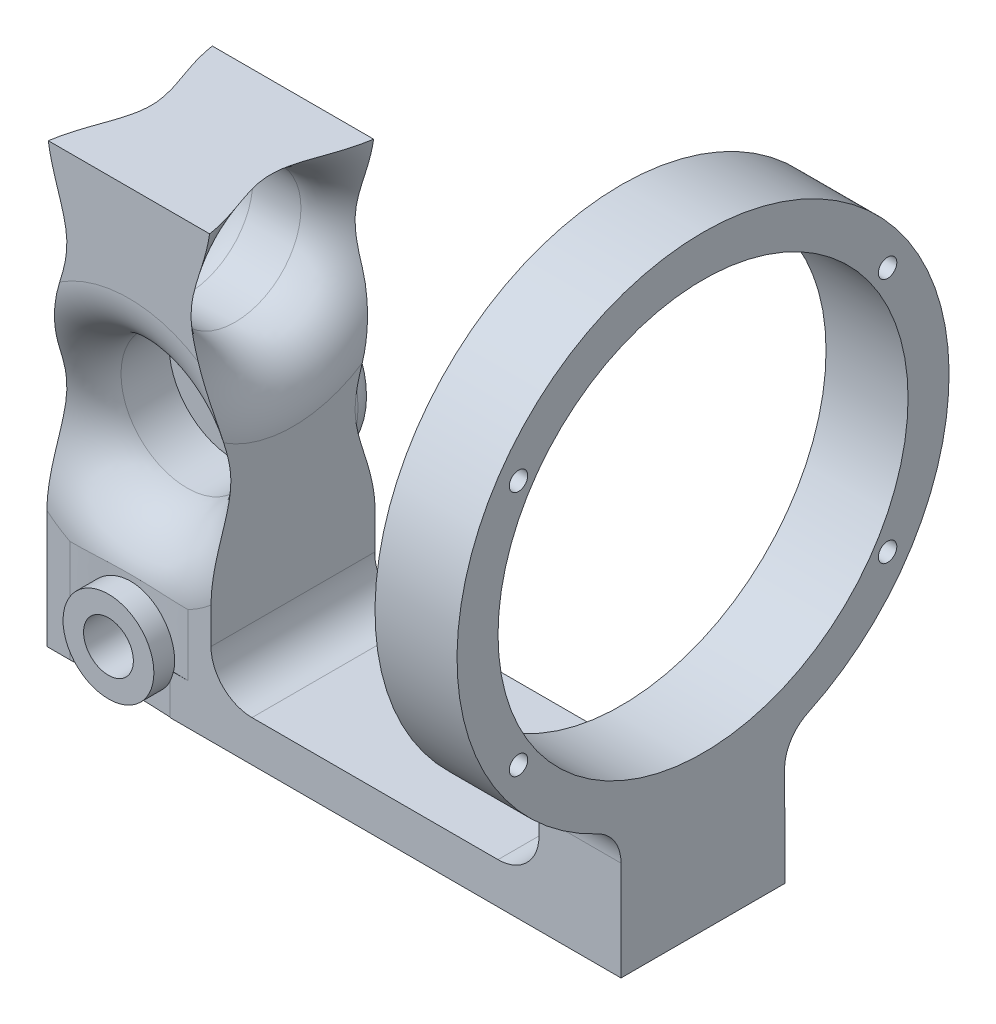
SolidWorks part; units mm, degrees
other "Markup1"
sketch "Sketch4" plane through (29.9294, 37, -10) normal (0.6492, 0.1556, -0.7445) x (-0.7605, 0.1488, -0.632)
ref_plane "Front Plane" through (0, 0, 0) normal (0, 0, 1) x (1, 0, 0)
ref_plane "Top Plane" through (0, 0, 0) normal (0, 1, 0) x (1, 0, 0)
ref_plane "Right Plane" through (0, 0, 0) normal (1, 0, 0) x (0, 0, -1)
sketch "Sketch1" plane through (0, 0, 0) normal (0, 0, 1) x (1, 0, 0)
  line L1 (20, -30) -> (-20, -30)
  line L2 (20, -30) -> (20, 30)
  line L3 (20, 30) -> (-20, 30)
  line L4 (-20, -30) -> (-20, 30)
  circle A0 centre (0, -17.5) radius 11.05
  point P0 (0, 0)
  dimension "D4" = 22.1
  dimension "D1" = 40
  dimension "D2" = 17.5
  dimension "D3" = 60
extrude "Boss-Extrude1" add sketch "Sketch1" along normal blind 40
sketch "Sketch2" plane through (-20, 0, 0) normal (-1, 0, 0) x (0, 0, 1)
  line L0 (40, 30) -> (0, 30) construction
  circle A0 centre (20, 17.5) radius 11.05
  dimension "D1" = 22.1
  dimension "D2" = 12.5
extrude "Cut-Extrude1" cut sketch "Sketch2" against normal blind 40 contours A0
fillet "Fillet1" radius 4 4 edges at (11.05, -17.5, 0) (11.05, -17.5, 40) (-20, 17.5, 31.05) (20, 17.5, 31.05)
sketch "Sketch3" plane through (0, 30, 0) normal (0, 1, 0) x (1, 0, 0)
  line L0 (-20, -20) -> (19.8588, -20)
  line L1 (-20, -4.95) -> (-20, -35.05) construction
  line L3 (29.9294, -50) -> (-30.0706, -50)
  line L4 (29.9294, -50) -> (29.9294, 10)
  line L5 (29.9294, 10) -> (-30.0706, 10)
  line L6 (-30.0706, -50) -> (-30.0706, 10)
  line L7 (29.9294, -50) -> (-30.0706, 10) construction
  line L8 (29.9294, 10) -> (-30.0706, -50) construction
  point P4 (-0.0706, -20)
  dimension "D1" = 60
extrude "Boss-Extrude2" add sketch "Sketch3" along normal blind 7
chamfer "Chamfer1" distance 1.75 angle 45 12 edges at (-0.0706, 37, -10) (-0.0706, 30, -10) (29.9294, 37, 20) (29.9294, 33.5, -10) (29.9294, 30, 20) (-0.0706, 37, 50) (29.9294, 33.5, 50) (-0.0706, 30, 50) (-30.0706, 33.5, -10) (-30.0706, 37, 20) (-30.0706, 33.5, 50) (-30.0706, 30, 20)
sketch "Sketch6" plane through (0, 30, 0) normal (0, -1, 0) x (-1, 0, 0)
  line L0 (20, -40) -> (-20, -40)
  line L1 (-20, -40) -> (-20, 0)
  line L2 (-20, 0) -> (20, 0)
  line L3 (20, 0) -> (20, -40)
  line L4 (36.5937, -52.5638) -> (-35.2538, -52.5638)
  line L5 (-35.2538, -52.5638) -> (-35.2538, 13.1087)
  line L6 (-35.2538, 13.1087) -> (36.5937, 13.1087)
  line L7 (36.5937, 13.1087) -> (36.5937, -52.5638)
extrude "Cut-Extrude3" cut sketch "Sketch6" against normal blind 100
sketch "Sketch7" plane through (20, 0, 0) normal (1, 0, 0) x (0, 0, -1)
  circle A0 centre (-20, 17.5) radius 16.05
  dimension "D1" = 32.1
extrude "Cut-Extrude4" cut sketch "Sketch7" against normal blind 100
fillet "Fillet2" radius 15 2 edges at (-20, 17.5, 3.95) (20, 17.5, 3.95)
sketch "Sketch12" plane through (0, -30, 0) normal (0, -1, 0) x (-1, 0, 0)
  line L0 (20, -40) -> (-20, -40)
  line L1 (-20, -40) -> (-20, 0)
  line L2 (-20, 0) -> (20, 0)
  line L3 (20, 0) -> (20, -40)
sketch "Sketch14" plane through (0, -30, 0) normal (0, -1, 0) x (-1, 0, 0)
  line L0 (20, -40) -> (-20, -40)
  line L1 (-20, -40) -> (-20, 0)
  line L2 (-20, 0) -> (20, 0)
  line L3 (20, 0) -> (20, -40)
extrude "Boss-Extrude5" add sketch "Sketch14" along normal blind 15
sketch "Sketch15" plane through (0, 0, 40) normal (0, 0, 1) x (1, 0, 0)
  circle A0 centre (0, -17.5) radius 16.05
  dimension "D1" = 32.1
extrude "Cut-Extrude7" cut sketch "Sketch15" against normal blind 100
fillet "Fillet3" radius 15 2 edges at (16.05, -17.5, 0) (16.05, -17.5, 40)
sketch "Sketch20" plane through (0, -45, 0) normal (0, -1, 0) x (-1, 0, 0)
  line L0 (20, 0) -> (-20, -40)
  line L2 (20, -40) -> (-20, 0)
  line L4 (20, 0) -> (-20, 0)
  line L5 (20, 0) -> (20, -40)
  line L6 (20, -40) -> (-20, -40)
  line L7 (-20, 0) -> (-20, -40)
  line L8 (20, 0) -> (-20, -40) construction
  line L9 (20, -40) -> (-20, 0) construction
  point P5 (0, -20)
extrude "Boss-Extrude7" add sketch "Sketch20" along normal blind 25
sketch "Sketch21" plane through (0, 0, 40) normal (0, 0, 1) x (1, 0, 0)
  line L0 (0, -57.5) -> (0, -45)
  line L1 (0, -57.5) -> (0, -70)
  line L2 (-14.4171, -70) -> (14.4171, -70) construction
  circle A0 centre (0, -57.5) radius 6.05
  spline S0 degree 3 poles (14.4171, -45) (12.0121, -45) (9.6108, -45) (6.0082, -45) (3.6062, -45) (1.2025, -45) (-1.2025, -45) (-3.6062, -45) (-6.0082, -45) (-9.6108, -45) (-12.0121, -45) (-14.4171, -45) knots 0 0 0 0 0.25 0.25 0.375 0.5 0.5 0.625 0.75 0.75 1 1 1 1 construction
  dimension "D1" = 12.1
extrude "Cut-Extrude11" cut sketch "Sketch21" against normal blind 10 contours L0 A0 L1 | L1 A0 L0
sketch "Sketch22" plane through (20, 0, 0) normal (1, 0, 0) x (0, 0, -1)
  line L0 (0, -70) -> (-40, -70) construction
  line L1 (0, -70) -> (0, -41.2508) construction
  line L2 (-40, -45) -> (0, -45)
  line L3 (-40, -70) -> (-40, -41.2508) construction
  line L4 (-20, -45) -> (-20, -57.5)
  line L5 (-20, -57.5) -> (0, -57.5)
  circle A1 centre (-20, -57.5) radius 6.05
  dimension "D1" = 12.1
  dimension "D2" = 25
  dimension "D3" = 12.5
  dimension "D4" = 20
extrude "Cut-Extrude12" cut sketch "Sketch22" against normal blind 10 contours L5 A1 L4 | L4 A1 L5
sketch "Sketch23" plane through (0, 0, 0) normal (0, 0, -1) x (-1, 0, 0)
  line L0 (20, -41.2508) -> (20, -70) construction
  circle A0 centre (0, -57.5) radius 6.05
  dimension "D3" = 12.1
  dimension "D1" = 20
  dimension "D2" = 12.5
extrude "Cut-Extrude18" cut sketch "Sketch23" against normal blind 10
sketch "Sketch24" plane through (-20, 0, 0) normal (-1, 0, 0) x (0, 0, 1)
  line L0 (40, -70) -> (0, -70) construction
  circle A0 centre (20, -57.5) radius 6.05
  dimension "D1" = 12.1
  dimension "D2" = 12.5
extrude "Cut-Extrude19" cut sketch "Sketch24" against normal blind 10
sketch "Sketch25" plane through (20, 0, 0) normal (1, 0, 0) x (0, 0, -1)
  circle A0 centre (-20, 17.5) radius 50
  circle A1 centre (-20, 17.5) radius 60
  dimension "D1" = 100
  dimension "D2" = 10
extrude "Boss-Extrude8" add sketch "Sketch25" along normal blind 20 from offset 80 separate body
sketch "Sketch26" plane through (120, 0, 0) normal (1, 0, 0) x (0, 0, -1)
  line L0 (-40, -70) -> (0, -70)
  line L1 (0, -70) -> (-0.1452, -38.4492)
  line L2 (-40, -70) -> (-40, -38.4492)
  line L3 (-40, -38.4492) -> (-0.1452, -38.4492)
  spline S0 degree 3 poles (-3.1059, -8.5517) (-3.5245, -9.8859) (-3.9276, -11.2231) (-4.5568, -13.9327) (-4.7791, -15.3059) (-4.8543, -17.0624) (-4.8594, -17.417) (-4.849, -18.1218) (-4.8337, -18.4722) (-4.7593, -19.5181) (-4.6714, -20.208) (-4.3178, -22.2606) (-3.9628, -23.6062) (-3.1703, -26.2815) (-2.7339, -27.6113) (-1.8977, -30.2783) (-1.4974, -31.6155) (-0.4659, -35.6628) (0, -38.4078) (0, -41.2508) knots 0 0 0 0 0.125 0.125 0.25 0.25 0.28125 0.28125 0.3125 0.3125 0.375 0.375 0.5 0.5 0.625 0.625 0.75 0.75 1 1 1 1 construction
extrude "Boss-Extrude9" add sketch "Sketch26" against normal blind 20
sketch "Sketch27" plane through (120, 0, 0) normal (1, 0, 0) x (0, 0, -1)
  line L6 (-40, -60) -> (-0.046, -60)
  line L7 (-40, -39.0685) -> (-40, -70) construction
  line L8 (0, -70) -> (-0.1421, -39.1186) construction
  line L9 (-40, -70) -> (0, -70) construction
  line L10 (-40, -60) -> (-40, -70)
  line L11 (-40, -70) -> (0, -70)
  line L12 (0, -70) -> (-0.046, -60)
  dimension "D1" = 10
extrude "Boss-Extrude11" add sketch "Sketch27" against normal blind 110
sketch "Sketch28" plane through (20, 0, 0) normal (1, 0, 0) x (0, 0, -1)
  circle A0 centre (-20, -57.5) radius 6.05
extrude "Boss-Extrude12" add sketch "Sketch28" against normal blind 30
sketch "Sketch29" plane through (120, 0, 0) normal (1, 0, 0) x (0, 0, -1)
  line L0 (-20, 17.5) -> (-20, 47.5)
  line L1 (25, -12.5) -> (-65, -12.5)
  line L2 (25, -12.5) -> (25, 47.5)
  line L3 (25, 47.5) -> (-65, 47.5)
  line L4 (-65, -12.5) -> (-65, 47.5)
  line L5 (25, -12.5) -> (-65, 47.5) construction
  line L6 (25, 47.5) -> (-65, -12.5) construction
  line L7 (-20, 47.5) -> (-20, 17.5)
  line L8 (-65, 17.5) -> (25, 17.5)
  circle A0 centre (-65, 47.5) radius 2.25
  circle A1 centre (25, 47.5) radius 2.25
  circle A2 centre (25, -12.5) radius 2.25
  circle A3 centre (-65, -12.5) radius 2.25
  point P0 (-20, 17.5)
  dimension "D3" = 4.5
  dimension "D1" = 90
  dimension "D2" = 60
extrude "Cut-Extrude20" cut sketch "Sketch29" against normal blind 20 and the other way through all contours A0 | A1 | A2 | A3
fillet "Fillet4" radius 10 3 edges at (100, -60, 20.023) (110, -39.0685, 40) (110, -39.1186, 0.1421)
fillet "Fillet5" radius 10 1 edges at (20, -60, 20.023)
sketch "Sketch30" plane through (0, 0, 0) normal (0, 0, -1) x (-1, 0, 0)
  line L0 (-14.4171, -60) -> (-14.4171, -70)
  line L1 (-14.4171, -70) -> (-14.4171, -45) construction
  line L2 (-14.4171, -70) -> (-10, -70)
  line L3 (-10, -70) -> (-10, -60)
  line L4 (-10, -60) -> (-14.4171, -60)
  dimension "D1" = 10
extrude "Boss-Extrude13" add sketch "Sketch30" against normal blind 9.6
sketch "Sketch31" plane through (0, 0, 0) normal (0, 0, -1) x (-1, 0, 0)
  circle A0 centre (0, -17.5) radius 16.05
  circle A1 centre (0, -17.5) radius 16.075
  dimension "D1" = 32.15
extrude "Cut-Extrude21" cut sketch "Sketch31" against normal blind 50
sketch "Sketch32" plane through (20, 0, 0) normal (1, 0, 0) x (0, 0, -1)
  circle A0 centre (-20, 17.5) radius 16.05
  circle A1 centre (-20, 17.5) radius 16.075
  dimension "D1" = 32.15
extrude "Cut-Extrude22" cut sketch "Sketch32" against normal blind 50
ref_plane "Plane1" through (0, 0, 14.1343) normal (0, 0, 1) x (1, 0, 0)
sketch "Sketch34" plane through (0, 0, 14.1343) normal (0, 0, 1) x (1, 0, 0)
  line L0 (20, -41.2508) -> (20, -8.5517) construction
  line L1 (-20, -8.5517) -> (-20, -41.2508) construction
  circle A1 centre (0, -17.5) radius 20
extrude "Boss-Extrude22" add sketch "Sketch34" against normal blind 15
fillet "Fillet7" radius 5 1 edges at (20, -17.5, -0.8657)
sketch "Sketch45" plane through (0, 0, 30) normal (0, 0, 1) x (1, 0, 0)
  circle A0 centre (0, -57.5) radius 6.075
  dimension "D1" = 12.15
extrude "Cut-Extrude24" cut sketch "Sketch45" along normal blind 10
sketch "Sketch46" plane through (-10, 0, 0) normal (-1, 0, 0) x (0, 0, 1)
  circle A0 centre (20, -57.5) radius 6.075
  dimension "D1" = 12.15
extrude "Cut-Extrude25" cut sketch "Sketch46" along normal blind 10
sketch "Sketch48" plane through (0, 0, 40) normal (0, 0, 1) x (1, 0, 0)
  circle A0 centre (0, -57.5) radius 6.075
  circle A1 centre (0, -57.5) radius 11.075
  dimension "D1" = 5
extrude "Boss-Extrude24" add sketch "Sketch48" along normal mid plane 10
sketch "Sketch49" plane through (-20, 0, 0) normal (-1, 0, 0) x (0, 0, 1)
  circle A0 centre (20, -57.5) radius 6.075
  circle A1 centre (20, -57.5) radius 11.075
  dimension "D1" = 5
extrude "Boss-Extrude25" add sketch "Sketch49" along normal mid plane 10
